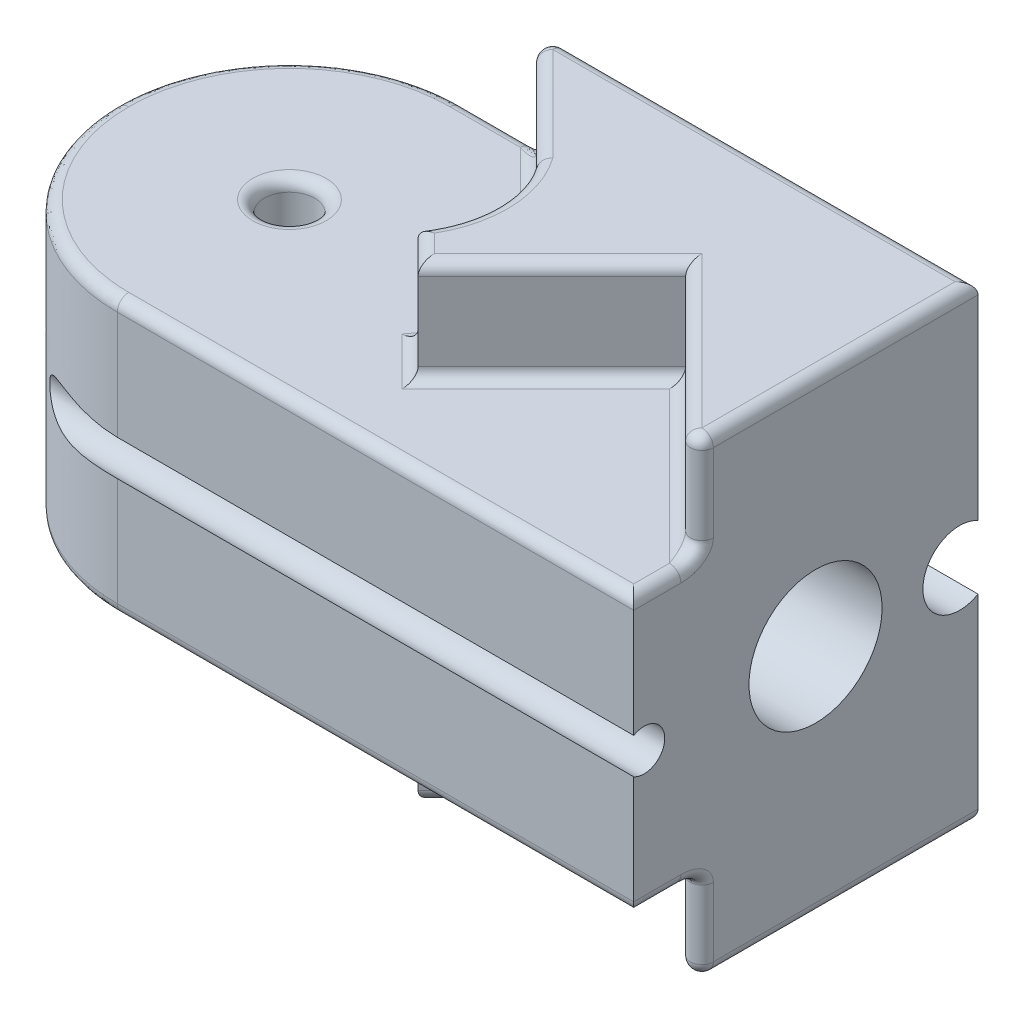
SolidWorks part; units mm, degrees
ref_plane "Front Plane" through (0, 0, 0) normal (0, 0, 1) x (1, 0, 0)
ref_plane "Top Plane" through (0, 0, 0) normal (0, 1, 0) x (1, 0, 0)
ref_plane "Right Plane" through (0, 0, 0) normal (1, 0, 0) x (0, 0, -1)
sketch "Sketch1" plane through (0, 0, 0) normal (0, 1, 0) x (1, 0, 0)
  line L0 (0, 0) -> (15, 0)
  line L1 (15, 0) -> (15, 20)
  line L2 (15, 20) -> (-7.5, 20)
  line L3 (0, 0) -> (0, 5)
  line L4 (0, 5) -> (-7.5, 5)
  line L6 (-7.5, 12.5) -> (-15, 12.5) construction
  line L7 (-7.5, 20) -> (-7.5, 12.5) construction
  ellipse E0 centre (-7.5, 12.5) end of major axis (-7.5, 20) minor radius 7.5 (-15, 12.5) -> (-7.5, 20) cw
  ellipse E1 centre (-7.5, 12.5) end of major axis (0, 12.5) minor radius 7.5 (-15, 12.5) -> (-7.5, 5) ccw
  dimension "D1" = 22.5
  dimension "D2" = 20
  dimension "D3" = 7.5
  dimension "D4" = 7.5
  dimension "D5" = 15
  dimension "D6" = 15
  dimension "D7" = 5
extrude "Boss-Extrude1" add sketch "Sketch1" along normal blind 16
ref_plane "Plane1" through (0, 8, 0) normal (0, 1, 0) x (1, 0, 0)
sketch "Sketch4" plane through (0, 0, 0) normal (0, 1, 0) x (1, 0, 0)
  line L0 (-7.5, 20) -> (-7.5, 12.5) construction
  line L1 (7.9289, 14.3332) -> (2.1004, 8.5047)
  line L2 (2.1004, 8.5047) -> (0.6862, 9.9189)
  line L4 (15, 0) -> (15, 20) construction
  line L7 (0.6862, 15.0811) -> (-4.2327, 20)
  line L8 (15, 20) -> (-7.5, 20) construction
  line L10 (-7.5, 5) -> (0, 5)
  line L11 (0, 5) -> (0, 0)
  line L13 (7.9289, 14.3332) -> (15, 7.2622)
  line L15 (0, 0) -> (15, 0)
  line L16 (15, 0) -> (15, 7.2622)
  line L19 (-7.5, 20) -> (-4.2327, 20)
  circle A0 centre (-7.5, 12.5) radius 7.5 construction
  arc A1 (0.6862, 15.0811) -> (0.6862, 9.9189) centre (-3, 12.5) cw
  ellipse E0 centre (-7.5, 12.5) end of major axis (-15, 12.5) minor radius 7.5 (-7.5, 20) -> (-7.5, 5) ccw
  dimension "D1" = 4.5
  dimension "D2" = 4.5
  dimension "D3" = 70
  dimension "D4" = 45
  dimension "D5" = 2
  dimension "D6" = 10
extrude "Cut-Extrude1" cut sketch "Sketch4" along normal blind 4
ref_plane "Plane2" through (0, 26, 0) normal (0, 1, 0) x (1, 0, 0)
sketch "Sketch5" plane through (0, 26, 0) normal (0, 1, 0) x (1, 0, 0)
  line L20 (7.9289, 14.3332) -> (15, 7.2622)
  line L21 (2.1004, 8.5047) -> (7.9289, 14.3332)
  line L22 (0.6862, 9.9189) -> (2.1004, 8.5047)
  line L23 (-4.2327, 20) -> (0.6862, 15.0811)
  line L24 (15, 20) -> (-4.2327, 20)
  line L25 (15, 7.2622) -> (15, 20)
  line L26 (7.9289, 14.3332) -> (15, 7.2622)
  line L27 (2.1004, 8.5047) -> (7.9289, 14.3332)
  line L28 (0.6862, 9.9189) -> (2.1004, 8.5047)
  line L29 (-4.2327, 20) -> (0.6862, 15.0811)
  line L30 (15, 20) -> (-4.2327, 20)
  line L31 (15, 7.2622) -> (15, 20)
  arc A2 (0.6862, 9.9189) -> (0.6862, 15.0811) centre (-3, 12.5) ccw
  arc A3 (0.6862, 9.9189) -> (0.6862, 15.0811) centre (-3, 12.5) ccw
  dimension "D1" = 0
extrude "Cut-Extrude2" [suppressed] cut sketch "Sketch5" against normal blind 14
sketch "Sketch6" plane through (0, 0, 0) normal (1, 0, 0) x (0, 0, -1)
  line L0 (0, 10) -> (0, 10.5)
  line L1 (0, 16) -> (0, 4) construction
  line L2 (0, 10) -> (0, 5.5)
  line L3 (0, 10.5) -> (4.5941, 10.5)
  line L4 (0, 5.5) -> (4.5941, 5.5)
  line L5 (4.5941, 10.5) -> (4.5941, 5.5)
extrude "Cut-Extrude3" cut sketch "Sketch6" along normal through all
sketch "Sketch7" [suppressed] plane through (0, 8, 0) normal (0, 1, 0) x (1, 0, 0)
  line L0 (7.5, 0) -> (7.5, 2.7594) construction
  line L1 (0, 0) -> (15, 0) construction
  circle A0 centre (7.5, 2.7594) radius 1
extrude "Cut-Extrude4" [suppressed] cut sketch "Sketch7" against normal through all both and the other way through all
sketch "Sketch8" [suppressed] plane through (0, 8, 0) normal (0, 1, 0) x (1, 0, 0)
  line L0 (-7.5, 20) -> (-7.36, 12.5013) construction
  circle A0 centre (-7.36, 12.5013) radius 1.1
extrude "Cut-Extrude5" [suppressed] cut sketch "Sketch8" against normal through all both and the other way through all
fillet "Fillet2" [suppressed] radius 0.5
fillet "Fillet3" [suppressed] radius 0.5
sketch "Sketch9" [suppressed] plane through (0, 8, 0) normal (0, 1, 0) x (1, 0, 0)
  line L0 (0, 5) -> (3.9965, 5) construction
  line L1 (0, 0) -> (15, 0) construction
  line L2 (0, 5) -> (0, 0)
  line L3 (0, 0) -> (3.9965, 0)
  ellipse E0 centre (3.9965, 5) end of major axis (3.9965, 0) minor radius 3.9965 (3.9965, 0) -> (0, 5) cw
extrude "Cut-Extrude6" [suppressed] cut sketch "Sketch9" against normal through all both and the other way through all
fillet "Fillet4" [suppressed] radius 0.5
sketch "Sketch10" [suppressed] plane through (0, 8, 0) normal (0, 1, 0) x (1, 0, 0)
  line L0 (-14.36, 12.5013) -> (-15, 12.5) construction
  line L1 (-7.5, 12.5) -> (-7.5, 19.5) construction
  line L2 (-7.36, 12.5013) -> (-14.36, 12.5013) construction
  line L3 (-7.5, 20) -> (-7.5, 19.4989)
  line L4 (-7.5, 5.5011) -> (-7.5, 5)
  ellipse E0 centre (-7.5, 12.5) end of major axis (-7.4987, 19.4989) minor radius 6.86 (-7.5, 19.4989) -> (-7.5, 5.5011) ccw
  ellipse E1 centre (-7.5, 12.5) end of major axis (-15, 12.5) minor radius 7.5 (-7.5, 20) -> (-7.5, 5) ccw
extrude "Cut-Extrude7" [suppressed] cut sketch "Sketch10" against normal mid plane 1
chamfer "Chamfer1" [suppressed] distance 1 angle 75
chamfer "Chamfer2" [suppressed] distance 1.75 angle 15
scale "Scale1" [suppressed]
ref_plane "symmetry_plane" [suppressed] through (0, 8.75, 0) normal (0, 1, 0) x (1, 0, 0)
sketch "Sketch11" [suppressed] plane through (0, 4.35, 0) normal (0, -1, 0) x (1, 0, 0)
  line L0 (0, -5) -> (15, -5)
  line L1 (0, -5) -> (0, 0.0084)
  line L2 (15, -5) -> (15, 0.0084)
  line L3 (0, 0.0084) -> (15, 0.0084)
  line L4 (15, 0) -> (15, -7.2622) construction
extrude "Cut-Extrude8" [suppressed] cut sketch "Sketch11" against normal through all both and the other way through all
ref_plane "mirror_plane" through (0, 10, 0) normal (0, -1, 0) x (-1, 0, 0)
sketch "Sketch12" plane through (0, 16, 0) normal (0, 1, 0) x (1, 0, 0)
  line L18 (7.9289, 14.3332) -> (15, 7.2622)
  line L19 (2.1004, 8.5047) -> (7.9289, 14.3332)
  line L20 (0.6862, 9.9189) -> (2.1004, 8.5047)
  line L21 (-4.2327, 20) -> (0.6862, 15.0811)
  line L22 (15, 20) -> (-4.2327, 20)
  line L23 (15, 7.2622) -> (15, 20)
  line L24 (7.9289, 14.3332) -> (15, 7.2622)
  line L25 (2.1004, 8.5047) -> (7.9289, 14.3332)
  line L26 (0.6862, 9.9189) -> (2.1004, 8.5047)
  line L27 (-4.2327, 20) -> (0.6862, 15.0811)
  line L28 (15, 20) -> (-4.2327, 20)
  line L29 (15, 7.2622) -> (15, 20)
  arc A3 (0.6862, 9.9189) -> (0.6862, 15.0811) centre (-3, 12.5) ccw
  arc A4 (0.6862, 9.9189) -> (0.6862, 15.0811) centre (-3, 12.5) ccw
  dimension "D1" = 0
extrude "Boss-Extrude2" add sketch "Sketch12" along normal blind 4.4
sketch "Sketch13" plane through (0, 0, 0) normal (-1, 0, 0) x (0, 0, 1)
  line L8 (0, 5.5) -> (-4.5941, 5.5)
  line L9 (-4.5941, 5.5) -> (-4.5941, 10.5)
  line L10 (-4.5941, 10.5) -> (0, 10.5)
  line L11 (0, 10.5) -> (0, 16)
  line L12 (0, 16) -> (-5, 16)
  line L13 (-5, 16) -> (-5, 4)
  line L14 (-5, 4) -> (0, 4)
  line L15 (0, 4) -> (0, 5.5)
  line L16 (0, 5.5) -> (-4.5941, 5.5)
  line L17 (-4.5941, 5.5) -> (-4.5941, 10.5)
  line L18 (-4.5941, 10.5) -> (0, 10.5)
  line L19 (0, 10.5) -> (0, 16)
  line L20 (0, 16) -> (-5, 16)
  line L21 (-5, 16) -> (-5, 4)
  line L22 (-5, 4) -> (0, 4)
  line L23 (0, 4) -> (0, 5.5)
  dimension "D1" = 0
extrude "Cut-Extrude9" cut sketch "Sketch13" against normal through all both and the other way through all
sketch "Sketch14" plane through (0, 4, 0) normal (0, -1, 0) x (1, 0, 0)
  line L0 (-7.5, -5) -> (-7.5, -20)
  line L1 (-7.5, -20) -> (-7.5, -12.5)
  circle A0 centre (-7.5, -12.5) radius 1.1
  dimension "D1" = 2.2
extrude "Cut-Extrude10" cut sketch "Sketch14" against normal through all both and the other way through all contours L0 A0 | L0 A0 region at (-7.0331, 4, -12.5) region at (-7.9669, 4, -12.5)
ref_point "Point1"
sketch "Sketch15" plane through (15, 0, 0) normal (1, 0, 0) x (0, 0, -1)
  circle A0 centre (12.9217, 10.1811) radius 2.9
  dimension "D1" = 5.8
extrude "ruthex_m3_hole" cut sketch "Sketch15" against normal blind 8.3
fillet "Fillet5" radius 0.5 40 edges at (15, 2, -7.2622) (-4.2327, 2, -20) (-4.2327, 18.2, -20) (15, 18.2, -7.2622) (15, 0, -13.6311) (5.3836, 0, -20) (-1.7733, 0, -17.5405) (1.5, 0, -12.5) (1.3933, 0, -9.2118) (5.0147, 0, -11.419) (11.4645, 0, -10.7977) (11.4645, 20.4, -10.7977) (5.0147, 20.4, -11.419) (1.3933, 20.4, -9.2118) (1.5, 20.4, -12.5) (-1.7733, 20.4, -17.5405) (5.3836, 20.4, -20) (15, 20.4, -13.6311) (11.4645, 4, -10.7977) (5.0147, 4, -11.419) (1.3933, 4, -9.2118) (1.5, 4, -12.5) (-1.7733, 4, -17.5405) (15, 4, -6.1311) (-7.5, 4, -11.4) (-12.8033, 16, -7.1967) (-12.8033, 16, -17.8033) (-5.8664, 16, -20) (-1.7733, 16, -17.5405) (1.5, 16, -12.5) (1.3933, 16, -9.2118) (5.0147, 16, -11.419) (11.4645, 16, -10.7977) (15, 16, -6.1311) (3.75, 16, -5) (-7.5, 16, -11.4)
fillet "Fillet6" [suppressed] radius 2
sketch "Sketch16" plane through (15, 0, 0) normal (1, 0, 0) x (0, 0, -1)
  line L0 (5, 10) -> (20, 10) construction
  line L8 (8.4693, 3.5) -> (8.4693, 0.5)
  line L9 (8.4693, 0.5) -> (20, 0.5)
  line L10 (20, 0.5) -> (20, 19.9)
  line L11 (20, 19.9) -> (8.4693, 19.9)
  line L12 (8.4693, 19.9) -> (8.4693, 16.5)
  line L13 (7.0551, 15.5) -> (5, 15.5)
  line L14 (5, 15.5) -> (5, 4.5)
  line L15 (5, 4.5) -> (7.0551, 4.5)
  line L16 (8.4693, 3.5) -> (8.4693, 0.5)
  line L17 (8.4693, 0.5) -> (20, 0.5)
  line L18 (20, 0.5) -> (20, 19.9)
  line L19 (20, 19.9) -> (8.4693, 19.9)
  line L20 (8.4693, 19.9) -> (8.4693, 16.5)
  line L21 (7.0551, 15.5) -> (5, 15.5)
  line L22 (5, 15.5) -> (5, 4.5)
  line L23 (5, 4.5) -> (7.0551, 4.5)
  arc A0 (5, 10.7794) -> (5, 9.2206) centre (5.45, 10) cw
  arc A1 (20, 11.3856) -> (20, 8.6144) centre (19.2, 10) ccw
  ellipse E2 centre (7.0551, 16.5) end of major axis (5.6408, 16.5) minor radius 1 (7.0551, 15.5) -> (8.4693, 16.5) ccw
  ellipse E3 centre (7.0551, 3.5) end of major axis (8.4693, 3.5) minor radius 1 (8.4693, 3.5) -> (7.0551, 4.5) ccw
  ellipse E4 centre (7.0551, 16.5) end of major axis (5.6408, 16.5) minor radius 1 (7.0551, 15.5) -> (8.4693, 16.5) ccw
  ellipse E5 centre (7.0551, 3.5) end of major axis (8.4693, 3.5) minor radius 1 (8.4693, 3.5) -> (7.0551, 4.5) ccw
  line M14 (20, 0.5) -> (20, 19.9)
  line M19 (5, 15.5) -> (5, 4.5)
  dimension "D2" = 0.9
  dimension "D4" = 1.6
  dimension "D3" = 120
  dimension "D5" = 120
  dimension "D1" = 0
extrude "1.6mm_and_3mm_PTFE_tube_clamp_cutout" cut sketch "Sketch16" against normal through all contours L0 A0 M19 | L22 L0 A0 | A1 L0 M14 | L0 A1 L18 region at (15, 10.4006, -5.6042) region at (15, 9.5994, -5.6042) region at (15, 10.7122, -18.9259) region at (15, 9.2878, -18.9259)
ref_plane "mirror_plane_1" through (0, 0, -12.5) normal (0, 0, -1) x (-1, 0, 0)
